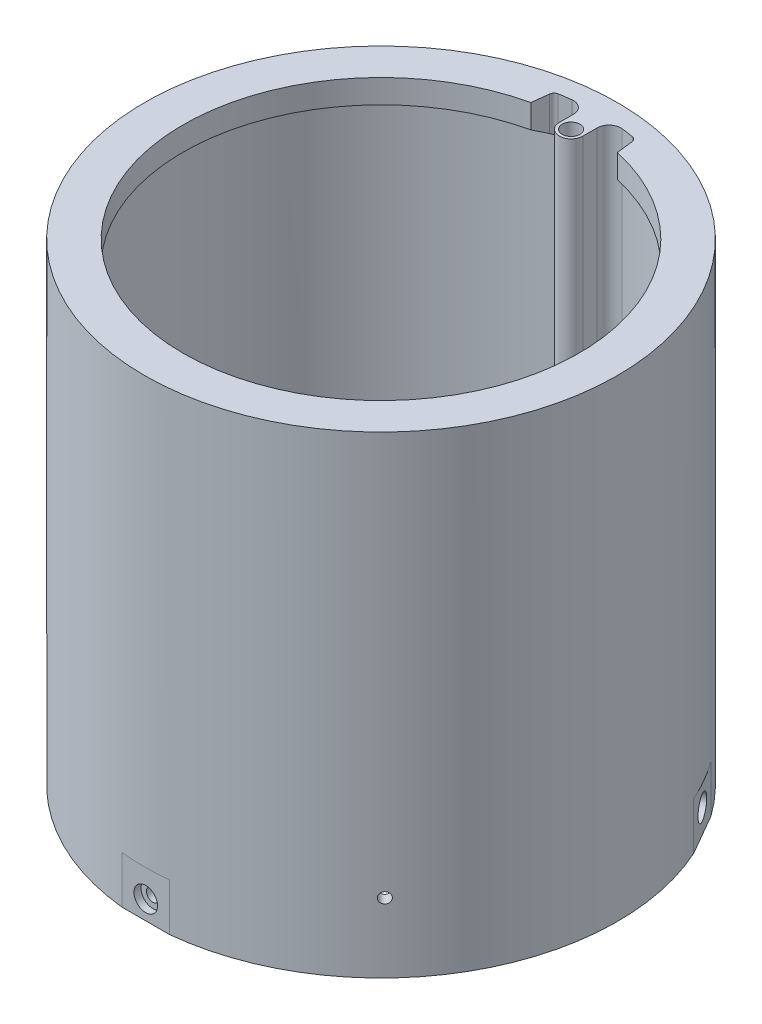
SolidWorks part; units mm, degrees
ref_plane "Piano frontale" through (0, 0, 0) normal (0, 0, 1) x (1, 0, 0)
ref_plane "Piano superiore" through (0, 0, 0) normal (0, 1, 0) x (1, 0, 0)
ref_plane "Piano destro" through (0, 0, 0) normal (1, 0, 0) x (0, 0, -1)
sketch "Schizzo1" plane through (0, 0, 0) normal (0, 1, 0) x (1, 0, 0)
  line L0 (-5, 80.4091) -> (-5, 91.864)
  line L1 (5, 80.4091) -> (5, 91.864)
  circle A0 centre (0, 0) radius 100
  arc A1 (-5, 91.864) -> (5, 91.864) centre (0, 0) ccw
  arc A2 (-5, 80.4091) -> (5, 80.4091) centre (0, 80.4091) ccw
  dimension "D1" = 200
  dimension "D2" = 184
  dimension "D4" = 10
  dimension "D3" = 11.4549
extrude "Estrusione-Estrusione1" add sketch "Schizzo1" along normal blind 200
fillet "Raccordo1" radius 5 2 edges at (-5, 100, -91.864) (5, 100, -91.864)
sketch "Schizzo2" plane through (0, 200, 0) normal (0, 1, 0) x (1, 0, 0)
  line L0 (-18.3, 81.675) -> (-17.2684, 90.3648)
  line L2 (-5, 80.4091) -> (-5, 86.4234) construction
  line L3 (18.3, 81.675) -> (17.2684, 90.3648)
  line L4 (5, 86.4234) -> (5, 80.4091) construction
  line L5 (-18.3, 81.675) -> (18.3, 81.675) construction
  line L6 (0, 0) -> (0, 81.675) construction
  arc A0 (-18.3, 81.675) -> (18.3, 81.675) centre (0, 0) ccw
  arc A3 (-10.5747, 91.3902) -> (10.5747, 91.3902) centre (0, 0) ccw construction
  circle A4 centre (0, 0) radius 92
  arc M13 (10.5747, 91.3902) -> (-10.5747, 91.3902) centre (0, 0) cw
  dimension "D1" = 167.4
  dimension "D2" = 6.77
  dimension "D3" = 6.77
  dimension "D4" = 36.6
extrude "Estrusione-Estrusione2" add sketch "Schizzo2" against normal blind 10 contours A0 L0 L3 M13 region at (0, 200, 86.2906)
chamfer "Smusso1" distance 5.5 angle 56.53 1 edges at (0, 190, 92) first distance on face at (0, 147.5, -45.1736)
fillet "Raccordo2" radius 2.1135 2 edges at (17.2684, 192.25, -90.3648) (-17.2684, 192.25, -90.3648)
sketch "Schizzo4" plane through (0, 200, 0) normal (0, 1, 0) x (1, 0, 0)
  line L0 (20.1776, 84.5858) -> (24.2009, 87.6231)
  line L1 (75.1117, 52.6034) -> (83.1117, 38.747)
  line L2 (8, -91.3504) -> (-8, -91.3504)
  line L3 (-83.1117, 38.747) -> (-75.1117, 52.6034)
  line L4 (-24.2009, 87.6231) -> (-20.1776, 84.5858)
  line L5 (-18.3, 81.675) -> (-17.4524, 88.8146) construction
  line L6 (18.3, 81.675) -> (17.4524, 88.8146) construction
  line L7 (-25, 88.2264) -> (25, 88.2264) construction
  line L8 (0, 88.2264) -> (0, 0) construction
  arc A0 (25.9724, 87.945) -> (75.1117, 52.6034) centre (0, 0) cw
  arc A1 (83.1117, 38.747) -> (8, -91.3504) centre (0, 0) cw
  arc A2 (-8, -91.3504) -> (-83.1117, 38.747) centre (0, 0) cw
  arc A3 (-75.1117, 52.6034) -> (-25.9724, 87.945) centre (0, 0) cw
  arc A4 (-20.1776, 84.5858) -> (-20.8836, 81.0529) centre (-21.3826, 82.9896) cw
  arc A5 (-20.8836, 81.0529) -> (20.8836, 81.0529) centre (0, 0) ccw
  arc A6 (20.8836, 81.0529) -> (20.1776, 84.5858) centre (21.3826, 82.9896) cw
  arc A7 (-18.3, 81.675) -> (18.3, 81.675) centre (0, 0) ccw construction
  arc A8 (24.2009, 87.6231) -> (25.9724, 87.945) centre (25.406, 86.0269) cw
  arc A9 (-24.2009, 87.6231) -> (-25.9724, 87.945) centre (-25.406, 86.0269) ccw
  dimension "D1" = 91.7
  dimension "D2" = 91.7
  dimension "D3" = 91.7
  dimension "D4" = 91.7
  dimension "D5" = 2
  dimension "D6" = 83.7
  dimension "D7" = 2
  dimension "D14" = 2
  dimension "D8" = 16
  dimension "D9" = 8
  dimension "D10" = 16
  dimension "D11" = 59.72
  dimension "D12" = 59.72
  dimension "D13" = 50
extrude "Estrusione-Estrusione4" [suppressed] add sketch "Schizzo4" along normal blind 20
sketch "Schizzo6" plane through (0, 0, 0) normal (0, -1, 0) x (1, 0, 0)
  circle A0 centre (0, -80.4091) radius 3.75
  dimension "D1" = 7.5
extrude "Taglio-Estrusione1" cut sketch "Schizzo6" against normal blind 200
sketch "Schizzo7" plane through (0, 0, 0) normal (0, -1, 0) x (1, 0, 0)
  line L0 (-10, 99.4987) -> (10, 99.4987)
  line L3 (0, 99.4987) -> (0, 0) construction
  line L4 (0, 0) -> (0, -100) construction
  line L5 (81.1684, -58.4096) -> (91.1684, -41.0891)
  line L6 (-91.1684, -41.0891) -> (-81.1684, -58.4096)
  line L7 (-86.1684, -49.7494) -> (0, 0) construction
  line L8 (0, 0) -> (86.1684, -49.7494) construction
  arc A0 (10, 99.4987) -> (-10, 99.4987) centre (0, 0) ccw
  arc A1 (-91.1684, -41.0891) -> (-81.1684, -58.4096) centre (0, 0) ccw
  arc A2 (10, 99.4987) -> (-10, 99.4987) centre (0, 0) ccw
  arc A3 (81.1684, -58.4096) -> (91.1684, -41.0891) centre (0, 0) ccw
  circle M13 centre (0, 0) radius 100
  dimension "D1" = 200
  dimension "D2" = 20
  dimension "D3" = 60
  dimension "D4" = 60
  dimension "D5" = 20
  dimension "D7" = 20
extrude "Taglio-Estrusione2" cut sketch "Schizzo7" against normal blind 20 contours L0 M13 | L5 M13 | L6 M13 region at (0, 0, 99.6993) region at (-86.3421, 0, -49.8496) region at (86.3421, 0, -49.8496)
hole_wizard "Foro lamato per Bullone M5 a testa esagonale-1" positions "Schizzo8" profile "Schizzo9" counterbore size "M5" standard "Ansi Metric"
sketch "Schizzo8" plane through (86.1684, 0, -49.7494) normal (0.866, 0, -0.5) x (-0.5, 0, -0.866)
  line L0 (10, 0) -> (-10, 0) construction
  line L1 (10, 20) -> (10, 0) construction
  point P0 (0, 10)
  dimension "D1" = 10
  dimension "D2" = 10
sketch "Schizzo9" plane through (86.1684, 10, -49.7494) normal (0, 1, 0) x (-0.5, 0, -0.866)
  line L0 (0, 0) -> (0, 31.6223)
  line L1 (0, 31.6223) -> (2.7, 30)
  line L2 (2.7, 30) -> (2.7, 3)
  line L3 (2.7, 3) -> (5, 3)
  line L4 (5, 3) -> (5, 0)
  line L5 (5, 0) -> (0, 0)
  line L10 (0, 31.6223) -> (-2.7, 30) construction
  line L11 (0, -6.35) -> (0, 107.95) construction
  dimension "Hole Dia." = 5.4
  dimension "Hole Depth" = 30
  dimension "C'Bore Dia." = 10
  dimension "C'Bore Depth" = 3
  dimension "Drill Angle" = 118
hole_wizard "Foro lamato per Bullone M5 a testa esagonale-2" positions "Schizzo10" profile "Schizzo11" counterbore size "M5" standard "Ansi Metric"
sketch "Schizzo10" plane through (-86.1684, 0, -49.7494) normal (-0.866, 0, -0.5) x (-0.5, 0, 0.866)
  line L0 (10, 20) -> (10, 0) construction
  line L1 (10, 0) -> (-10, 0) construction
  point P0 (0, 8)
  point P9 (7.6471, 11.5586)
  dimension "D1" = 10
  dimension "D2" = 8
sketch "Schizzo11" plane through (-86.1684, 8, -49.7494) normal (0, 1, 0) x (-0.5, 0, 0.866)
  line L0 (0, 0) -> (0, 31.6223)
  line L1 (0, 31.6223) -> (2.7, 30)
  line L2 (2.7, 30) -> (2.7, 3)
  line L3 (2.7, 3) -> (5, 3)
  line L4 (5, 3) -> (5, 0)
  line L5 (5, 0) -> (0, 0)
  line L10 (0, 31.6223) -> (-2.7, 30) construction
  line L11 (0, -6.35) -> (0, 107.95) construction
  dimension "Hole Dia." = 5.4
  dimension "Hole Depth" = 30
  dimension "C'Bore Dia." = 10
  dimension "C'Bore Depth" = 3
  dimension "Drill Angle" = 118
hole_wizard "Foro lamato per Bullone M5 a testa esagonale-3" positions "Schizzo12" profile "Schizzo13" counterbore size "M5" standard "Ansi Metric"
sketch "Schizzo12" plane through (0, 0, 99.4987) normal (0, 0, 1) x (1, 0, 0)
  line L0 (-10, 0) -> (10, 0) construction
  line L1 (10, 20) -> (10, 0) construction
  point P0 (0, 8)
  dimension "D1" = 8
  dimension "D2" = 10
sketch "Schizzo13" plane through (0, 8, 99.4987) normal (1, 0, 0) x (0, -1, 0)
  line L0 (0, 0) -> (0, 31.6223)
  line L1 (0, 31.6223) -> (2.7, 30)
  line L2 (2.7, 30) -> (2.7, 3)
  line L3 (2.7, 3) -> (5, 3)
  line L4 (5, 3) -> (5, 0)
  line L5 (5, 0) -> (0, 0)
  line L10 (0, 31.6223) -> (-2.7, 30) construction
  line L11 (0, -6.35) -> (0, 107.95) construction
  dimension "Hole Dia." = 5.4
  dimension "Hole Depth" = 30
  dimension "C'Bore Dia." = 10
  dimension "C'Bore Depth" = 3
  dimension "Drill Angle" = 118
hole_wizard "Foro lamato per Vite M4 a testa esagonale-1" positions "Schizzo3D1" profile "Schizzo14" counterbore size "M4" standard "Ansi Metric"
sketch3d "Schizzo3D1"
  line L0 (5, 200, -80.4091) -> (5, 0, -80.4091) construction
  point P0 (65.8012, 29.3853, 64.2978)
  point P2 (-62.6738, 46.1611, -67.3498)
  point P3 (-80.9074, 200, 21.4404)
  point P8 (64.9992, 57.8112, 65.1084)
  dimension "D1" = 156.9614
  dimension "D2" = 29.3853
sketch "Schizzo14" plane through (65.8012, 29.3853, 64.2978) normal (0, 1, 0) x (-0.6989, 0, 0.7152)
  line L0 (0, 0) -> (0, 31.3519)
  line L1 (0, 31.3519) -> (2.25, 30)
  line L2 (2.25, 30) -> (2.25, 3)
  line L3 (2.25, 3) -> (5, 3)
  line L4 (5, 3) -> (5, 0)
  line L5 (5, 0) -> (0, 0)
  line L10 (0, 31.3519) -> (-2.25, 30) construction
  line L11 (0, -6.35) -> (0, 107.95) construction
  dimension "Hole Dia." = 4.5
  dimension "Hole Depth" = 30
  dimension "C'Bore Dia." = 10
  dimension "C'Bore Depth" = 3
  dimension "Drill Angle" = 118
